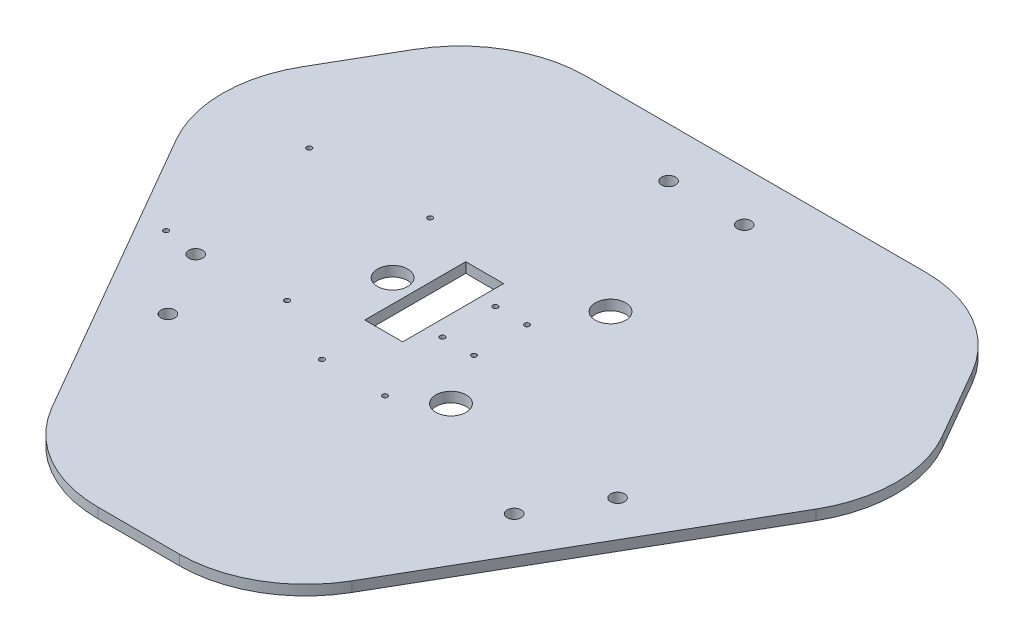
SolidWorks part; units mm, degrees
ref_plane "Front Plane" through (0, 0, 0) normal (0, 0, 1) x (1, 0, 0)
ref_plane "Top Plane" through (0, 0, 0) normal (0, 1, 0) x (1, 0, 0)
ref_plane "Right Plane" through (0, 0, 0) normal (1, 0, 0) x (0, 0, -1)
sketch "Sketch1" plane through (0, 0, 0) normal (0, 1, 0) x (1, 0, 0)
  line L1 (-50, 40) -> (50, 40)
  line L2 (-50, 40) -> (-50, -40)
  line L3 (-50, -40) -> (50, -40)
  line L4 (50, 40) -> (50, -40)
  line L5 (-50, 40) -> (50, -40) construction
  line L6 (-50, -40) -> (50, 40) construction
  point P0 (0, 0)
  dimension "D1" = 100
  dimension "D2" = 80
extrude "Boss-Extrude1" add sketch "Sketch1" along normal blind 4
sketch "Sketch2" plane through (0, 4, 0) normal (0, 1, 0) x (1, 0, 0)
  line L0 (-50, 40) -> (-50, -40) construction
  line L1 (-40, 30) -> (16.7, 30) construction
  line L2 (-40, 30) -> (-40, -17.9) construction
  line L3 (-40, -17.9) -> (16.7, -17.9) construction
  line L4 (16.7, 30) -> (16.7, -17.9) construction
  line L5 (50, 40) -> (-50, 40) construction
  circle A0 centre (-40, 30) radius 1
  circle A1 centre (16.7, 30) radius 1
  circle A2 centre (16.7, -17.9) radius 1
  circle A3 centre (-40, -17.9) radius 1
  dimension "D3" = 2
  dimension "D1" = 56.7
  dimension "D2" = 47.9
  dimension "D4" = 10
  dimension "D5" = 10
extrude "Cut-Extrude1" cut sketch "Sketch2" against normal through all
sketch "Sketch3" plane through (0, 4, 0) normal (0, 1, 0) x (1, 0, 0)
  line L0 (7.9935, -40) -> (50, -40)
  line L1 (-50, -40) -> (-32.0065, -40)
  line L2 (-50, -40) -> (-50, -80)
  line L3 (-50, -80) -> (50, -80)
  line L4 (50, -40) -> (50, -80)
  line L5 (50, -40) -> (50, 40) construction
  line L6 (-32.0065, -40) -> (-32.0065, -55)
  line L7 (-32.0065, -55) -> (7.9935, -55)
  line L8 (7.9935, -40) -> (7.9935, -55)
  dimension "D1" = 15
  dimension "D2" = 40
  dimension "D3" = 40
extrude "Boss-Extrude2" add sketch "Sketch3" against normal blind 4
sketch "Sketch4" plane through (0, 4, 0) normal (0, 1, 0) x (1, 0, 0)
  line L0 (-12.0065, -61.25) -> (-12.0065, -55) construction
  line L1 (-22.5065, -61.25) -> (-1.5065, -61.25) construction
  line L2 (-22.5065, -61.25) -> (-22.5065, -73.75) construction
  line L3 (-22.5065, -73.75) -> (-1.5065, -73.75) construction
  line L4 (-1.5065, -61.25) -> (-1.5065, -73.75) construction
  line L5 (7.9935, -55) -> (-32.0065, -55) construction
  line L6 (-32.0065, -55) -> (-32.0065, -80) construction
  line L7 (-50, -80) -> (50, -80) construction
  line L8 (-32.0065, -67.5) -> (-22.5065, -67.5) construction
  circle A0 centre (-22.5065, -61.25) radius 1
  circle A1 centre (-22.5065, -73.75) radius 1
  circle A2 centre (-1.5065, -73.75) radius 1
  circle A3 centre (-1.5065, -61.25) radius 1
  dimension "D3" = 2
  dimension "D1" = 21
  dimension "D2" = 12.5
extrude "Cut-Extrude2" cut sketch "Sketch4" against normal blind 4
sketch "Sketch5" plane through (0, 4, 0) normal (0, 1, 0) x (1, 0, 0)
  line L0 (30, -70) -> (30, -45) construction
  line L1 (-50, -80) -> (50, -80) construction
  line L2 (50, -80) -> (50, 40) construction
  circle A0 centre (30, -45) radius 1
  circle A1 centre (30, -70) radius 1
  circle A2 centre (-1.5065, -61.25) radius 1 construction
  dimension "D1" = 25
  dimension "D2" = 10
  dimension "D3" = 20
extrude "Cut-Extrude3" cut sketch "Sketch5" against normal blind 4
sketch "Sketch6" plane through (0, 4, 0) normal (0, 1, 0) x (1, 0, 0)
  line L0 (-12.0065, -40) -> (-12.0065, -50040) construction
  line L1 (-32.0065, -40) -> (7.9935, -40) construction
  circle A0 centre (-12.0065, -31) radius 6
  point P4 (-12.0065, -40)
  dimension "D1" = 12
  dimension "D2" = 9
extrude "Cut-Extrude4" cut sketch "Sketch6" against normal through all
sketch "Sketch7" plane through (0, 0, 0) normal (0, -1, 0) x (1, 0, 0)
  line L0 (-22.5065, 61.25) -> (-22.5065, 73.75) construction
  line L1 (-22.5065, 73.75) -> (-1.5065, 73.75) construction
  line L2 (-22.5065, 67.5) -> (49977.4935, 67.5) construction
  line L3 (-12.0065, 75.25) -> (-12.0065, -49924.75) construction
  line L4 (-146.2405, -40) -> (-50, -40)
  line L5 (148.2082, 5) -> (13.9742, 237.5)
  line L6 (-37.9873, 237.5) -> (-172.2212, 5)
  line L7 (50, -40) -> (-50, -40) construction
  line L8 (-12.0065, 67.5) -> (-105.1043, 121.25) construction
  line L9 (-50, -40) -> (-50, 80) construction
  line L10 (-50, 80) -> (50, 80) construction
  line L11 (50, 80) -> (50, -40) construction
  line L12 (-50, -40) -> (-50, 80)
  line L13 (-50, 80) -> (50, 80)
  line L14 (50, 80) -> (50, -40)
  line L15 (50, -40) -> (122.2274, -40)
  arc A0 (122.2274, -40) -> (148.2082, 5) centre (122.2274, -10) ccw
  arc A1 (13.9742, 237.5) -> (-37.9873, 237.5) centre (-12.0065, 222.5) ccw
  arc A2 (-146.2405, -40) -> (-172.2212, 5) centre (-146.2405, -10) cw
  point P8 (-22.5065, 67.5)
  point P11 (-12.0065, 73.75)
  point P12 (-12.0065, 67.5)
  point P28 (-12.0065, 282.5)
  dimension "D2" = 30
  dimension "D1" = 60
extrude "Boss-Extrude3" add sketch "Sketch7" against normal blind 4
sketch "Sketch8" plane through (0, 0, 0) normal (0, -1, 0) x (1, 0, 0)
  line L0 (-22.5065, 61.25) -> (-22.5065, 73.75) construction
  line L1 (-22.5065, 73.75) -> (-1.5065, 73.75) construction
  line L2 (-22.5065, 67.5) -> (49977.4935, 67.5) construction
  line L3 (-12.0065, 75.25) -> (-12.0065, 50075.25) construction
  line L4 (-11.357, 67.875) -> (43289.9132, 25067.875) construction
  line L5 (-12.6561, 67.875) -> (43288.6141, -24932.125) construction
  line L6 (122.2274, -40) -> (-146.2405, -40) construction
  circle A0 centre (-27.0065, -20.35) radius 2.75
  circle A1 centre (2.9935, -20.35) radius 2.75
  circle A2 centre (-80.5869, 124.4154) radius 2.75
  circle A3 centre (-95.5869, 98.4346) radius 2.75
  circle A4 centre (71.5738, 98.4346) radius 2.75
  circle A5 centre (56.5738, 124.4154) radius 2.75
  point P8 (-22.5065, 67.5)
  point P11 (-12.0065, 73.75)
  point P12 (-12.0065, 67.5)
  dimension "D3" = 5.5
  dimension "D1" = 60
  dimension "D2" = 60
  dimension "D4" = 16.9
  dimension "D5" = 30
extrude "Cut-Extrude5" cut sketch "Sketch8" against normal through all
sketch "Sketch9" plane through (0, 4, 0) normal (0, 1, 0) x (1, 0, 0)
  line L0 (-22.5065, -61.25) -> (-1.5065, -61.25) construction
  line L1 (-1.5065, -61.25) -> (-1.5065, -73.75) construction
  line L2 (-12.0065, -62.75) -> (-12.0065, -50062.75) construction
  line L3 (-1.5065, -67.5) -> (-50001.5065, -67.5) construction
  line L4 (-37.9873, -237.5) -> (-172.2212, -5) construction
  line L5 (122.2274, 40) -> (-146.2405, 40) construction
  line L6 (148.2082, -5) -> (13.9742, -237.5) construction
  line L7 (-153.202, -37.9423) -> (-108.202, 40)
  line L8 (-108.202, 40) -> (84.1889, 40)
  line L9 (84.1889, 40) -> (129.1889, -37.9423)
  line L10 (129.1889, -37.9423) -> (32.9935, -204.5577)
  line L11 (32.9935, -204.5577) -> (-57.0065, -204.5577)
  line L12 (-57.0065, -204.5577) -> (-153.202, -37.9423)
  circle A0 centre (-12.0065, -67.5) radius 144.2561 construction
  point P8 (-12.0065, -61.25)
  point P11 (-1.5065, -67.5)
  point P12 (-12.0065, -67.5)
  point P15 (-153.202, -37.9423)
  point P16 (-57.0065, -204.5577)
  point P19 (-108.202, 40)
  point P20 (84.1889, 40)
  point P23 (129.1889, -37.9423)
  point P24 (32.9935, -204.5577)
  arc M10 (148.2082, -5) -> (122.2274, 40) centre (122.2274, 10) ccw
  line M11 (122.2274, 40) -> (-146.2405, 40)
  arc M12 (-146.2405, 40) -> (-172.2212, -5) centre (-146.2405, 10) ccw
  line M13 (-172.2212, -5) -> (-37.9873, -237.5)
  arc M14 (-37.9873, -237.5) -> (13.9742, -237.5) centre (-12.0065, -222.5) ccw
  line M15 (13.9742, -237.5) -> (148.2082, -5)
  dimension "D1" = 90
extrude "Cut-Extrude6" cut sketch "Sketch9" against normal through all contours L11 M15 M13 M14 | L7 M13 M11 M12 | L9 M11 M15 M10 region at (-147.6818, 4, -10.8321) region at (-12.0065, 4, 224.1643) region at (123.6687, 4, -10.8321)
sketch "Sketch11" plane through (0, 4, 0) normal (0, 1, 0) x (1, 0, 0)
  line L6 (-32.0065, -40) -> (7.9935, -40) construction
  line L7 (-32.0065, -55) -> (-32.0065, -40) construction
  line L8 (7.9935, -55) -> (-32.0065, -55) construction
  line L9 (-32.0065, -40) -> (7.9935, -40) construction
  line L10 (-32.0065, -55) -> (-32.0065, -40) construction
  line L11 (7.9935, -55) -> (-32.0065, -55) construction
  line L12 (-22.5065, -73.75) -> (-1.5065, -61.25) construction
  line L13 (-11.2565, -68.25) -> (35344.0825, -35423.5891) construction
  line L14 (-12.0065, -67.5) -> (49987.9935, -67.5) construction
  line L15 (-24.5065, -87.5) -> (-24.5065, -47.5)
  line L16 (-24.5065, -47.5) -> (-39.5065, -47.5)
  line L17 (-39.5065, -47.5) -> (-39.5065, -87.5)
  line L30 (-39.5065, -87.5) -> (-24.5065, -87.5)
  circle A0 centre (-12.0065, -31) radius 6 construction
  circle A1 centre (-22.5065, -73.75) radius 1 construction
  circle A2 centre (-22.5065, -61.25) radius 1 construction
  circle A3 centre (-1.5065, -61.25) radius 1 construction
  circle A4 centre (-1.5065, -73.75) radius 1 construction
  circle A5 centre (30, -70) radius 1 construction
  circle A6 centre (30, -45) radius 1 construction
  circle A7 centre (16.7, -17.9) radius 1 construction
  circle A8 centre (-40, -17.9) radius 1 construction
  circle A9 centre (-40, 30) radius 1 construction
  circle A10 centre (16.7, 30) radius 1 construction
  circle A11 centre (-12.0065, -31) radius 6 construction
  circle A12 centre (-22.5065, -73.75) radius 1 construction
  circle A13 centre (-22.5065, -61.25) radius 1 construction
  circle A14 centre (-1.5065, -61.25) radius 1 construction
  circle A15 centre (-1.5065, -73.75) radius 1 construction
  circle A16 centre (30, -70) radius 1 construction
  circle A17 centre (30, -45) radius 1 construction
  circle A18 centre (16.7, -17.9) radius 1 construction
  circle A19 centre (-40, -17.9) radius 1 construction
  circle A20 centre (-40, 30) radius 1 construction
  circle A21 centre (16.7, 30) radius 1 construction
  circle A22 centre (-109.5065, -96.2065) radius 1
  circle A23 centre (-109.5065, -39.5065) radius 1
  circle A24 centre (-61.6065, -39.5065) radius 1
  circle A25 centre (-61.6065, -96.2065) radius 1
  circle A26 centre (-34.5065, -109.5065) radius 1
  circle A27 centre (-9.5065, -109.5065) radius 1
  circle A28 centre (-5.7565, -78) radius 1
  circle A29 centre (-18.2565, -78) radius 1
  circle A30 centre (-18.2565, -57) radius 1
  circle A31 centre (-5.7565, -57) radius 1
  circle A32 centre (-48.5065, -67.5) radius 6
  point P37 (-12.0065, -67.5)
  dimension "D1" = 45
extrude "Cut-Extrude7" cut sketch "Sketch11" against normal blind 4
sketch "Sketch14" plane through (0, 4, 0) normal (0, 1, 0) x (1, 0, 0)
  line L0 (-32.0065, -40) -> (7.9935, -40) construction
  line L1 (7.9935, -40) -> (7.9935, -55) construction
  line L2 (7.9935, -55) -> (-24.5065, -55) construction
  line L3 (-32.0065, -40) -> (7.9935, -40)
  line L4 (7.9935, -40) -> (7.9935, -55)
  line L5 (7.9935, -55) -> (-24.5065, -55)
  line L6 (-32.0065, -47.5) -> (-24.5065, -47.5)
  line L7 (-24.5065, -47.5) -> (-24.5065, -55)
  circle A0 centre (-22.5065, -61.25) radius 1 construction
  circle A1 centre (-1.5065, -61.25) radius 1 construction
  circle A2 centre (-22.5065, -73.75) radius 1 construction
  circle A3 centre (-1.5065, -73.75) radius 1 construction
  circle A4 centre (30, -70) radius 1 construction
  circle A5 centre (30, -45) radius 1 construction
  circle A6 centre (-12.0065, -31) radius 6 construction
  circle A7 centre (-40, -17.9) radius 1 construction
  circle A8 centre (16.7, -17.9) radius 1 construction
  circle A9 centre (-40, 30) radius 1 construction
  circle A10 centre (16.7, 30) radius 1 construction
  circle A11 centre (-22.5065, -61.25) radius 1
  circle A12 centre (-1.5065, -61.25) radius 1
  circle A13 centre (-22.5065, -73.75) radius 1
  circle A14 centre (-1.5065, -73.75) radius 1
  circle A15 centre (30, -70) radius 1
  circle A16 centre (30, -45) radius 1
  circle A17 centre (-12.0065, -31) radius 6
  circle A18 centre (-40, -17.9) radius 1
  circle A19 centre (16.7, -17.9) radius 1
  circle A20 centre (-40, 30) radius 1
  circle A21 centre (16.7, 30) radius 1
  line M3 (-32.0065, -47.5) -> (-32.0065, -40)
  line M4 (-32.0065, -40) -> (7.9935, -40)
  line M5 (7.9935, -40) -> (7.9935, -55)
  line M6 (7.9935, -55) -> (-24.5065, -55)
  circle M33 centre (-12.0065, -31) radius 6
  circle M34 centre (30, -70) radius 1
  circle M35 centre (30, -45) radius 1
  circle M36 centre (-1.5065, -61.25) radius 1
  circle M37 centre (-1.5065, -73.75) radius 1
  circle M38 centre (-22.5065, -73.75) radius 1
  circle M39 centre (-22.5065, -61.25) radius 1
  circle M40 centre (-40, -17.9) radius 1
  circle M41 centre (16.7, -17.9) radius 1
  circle M42 centre (16.7, 30) radius 1
  circle M43 centre (-40, 30) radius 1
extrude "Boss-Extrude5" add sketch "Sketch14" against normal blind 4 contours L6 L7 M6 M5 M4 M3 | M39 | M36 | M38 | M37 | M35 | M34 | M40 | M41 | M43 | M42 | M33 region at (-10.3255, 4, 47.1121) region at (-22.5065, 4, 61.25) region at (-1.5065, 4, 61.25) region at (-22.5065, 4, 73.75) region at (-1.5065, 4, 73.75) region at (30, 4, 70) region at (30, 4, 45) region at (-12.0065, 4, 31) region at (-40, 4, 17.9) region at (16.7, 4, 17.9) region at (-40, 4, -30) region at (16.7, 4, -30)
sketch "Sketch15" plane through (0, 4, 0) normal (0, 1, 0) x (1, 0, 0)
  line L0 (-18.2565, -57) -> (-5.7565, -78) construction
  circle A0 centre (-48.5065, -67.5) radius 6 construction
  circle A1 centre (-48.5065, -67.5) radius 6
  circle A2 centre (6.2435, -99.1099) radius 6
  circle A3 centre (6.2435, -35.8901) radius 6
  circle A4 centre (-12.0065, -67.5) radius 36.5 construction
  point P4 (-12.0065, -67.5)
  point P14 (-12.0065, -67.5)
  dimension "D1" = 3
extrude "Cut-Extrude8" cut sketch "Sketch15" against normal through all
fillet "Fillet1" radius 50 6 edges at (-57.0065, 2, 204.5577) (32.9935, 2, 204.5577) (129.1889, 2, 37.9423) (84.1889, 2, -40) (-108.202, 2, -40) (-153.202, 2, 37.9423)
sketch "Sketch16" plane through (0, 4, 0) normal (0, 1, 0) x (1, 0, 0)
  line L0 (-18.2565, -57) -> (-5.7565, -78)
  point P4 (-12.0065, -67.5)
ref_axis "Axis1" through (-12.0065, 4, 67.5) along (0, 1, 0)
